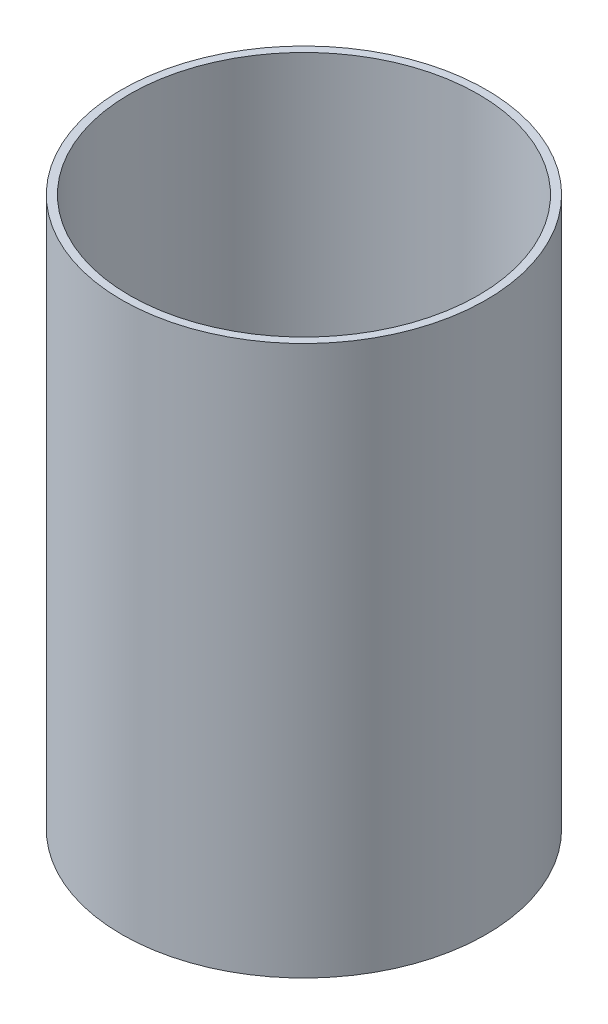
SolidWorks part; units mm, degrees
ref_plane "Front Plane" through (0, 0, 0) normal (0, 0, 1) x (1, 0, 0)
ref_plane "Top Plane" through (0, 0, 0) normal (0, 1, 0) x (1, 0, 0)
ref_plane "Right Plane" through (0, 0, 0) normal (1, 0, 0) x (0, 0, -1)
sketch "Sketch1" plane through (0, 0, 0) normal (0, 1, 0) x (1, 0, 0)
  circle A0 centre (0, 0) radius 117.602
  circle A1 centre (0, 0) radius 112.522
  dimension "D1" = 235.204
  dimension "D2" = 225.044
extrude "Boss-Extrude1" add sketch "Sketch1" along normal blind 354.6856
sketch "Sketch2" plane through (0, 0, 0) normal (0, -1, 0) x (1, 0, 0)
  circle A0 centre (0, 0) radius 117.602
  circle A1 centre (0, 0) radius 58.4604
extrude "Boss-Extrude2" add sketch "Sketch2" against normal blind 5.08
ref_plane "Plane1" through (-117.602, 0, 0) normal (-1, 0, 0) x (0, 0, 1)
sketch "Sketch3" plane through (-117.602, 0, 0) normal (-1, 0, 0) x (0, 0, 1)
  circle A0 centre (0, 36.5643) radius 25.4
extrude "Boss-Extrude3" add sketch "Sketch3" against normal up to surface (2.7757 mm away) up to face at (0, 0, 117.602)
sketch "Sketch4" plane through (-117.602, 0, 0) normal (-1, 0, 0) x (0, 0, 1)
  circle A0 centre (0, 36.5643) radius 25.4
extrude "Boss-Extrude4" add sketch "Sketch4" along normal blind 12.7
sketch "Sketch5" plane through (-130.302, 0, 0) normal (-1, 0, 0) x (0, 0, 1)
  circle A0 centre (0, 36.5643) radius 21.59
extrude "Cut-Extrude1" cut sketch "Sketch5" against normal up to next
